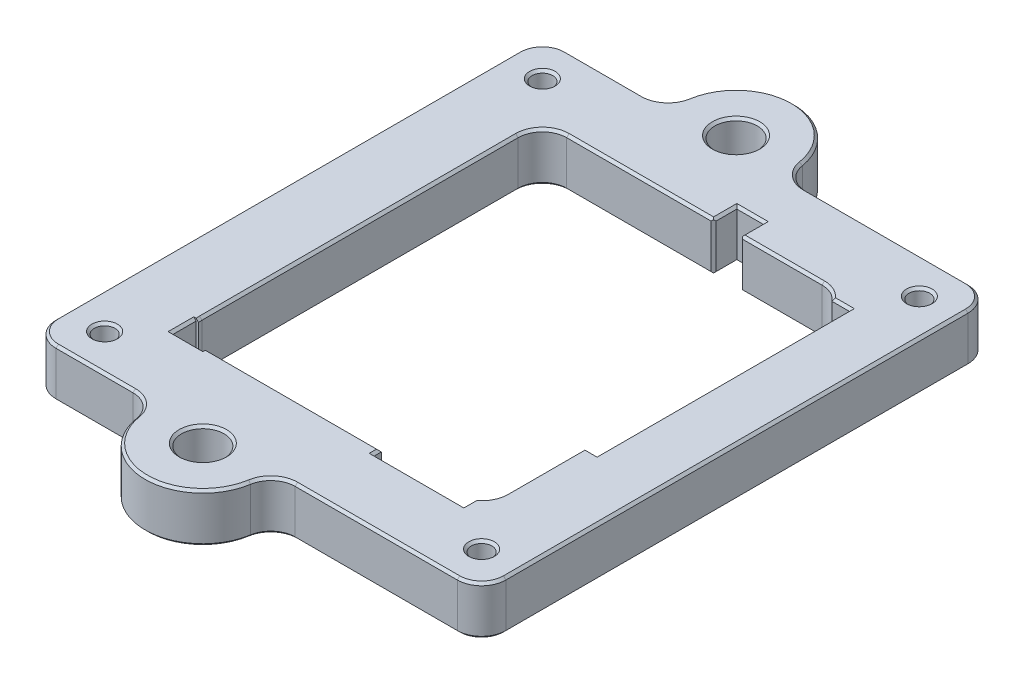
SolidWorks part; units mm, degrees
ref_plane "前视基准面" through (0, 0, 0) normal (0, 0, 1) x (1, 0, 0)
ref_plane "上视基准面" through (0, 0, 0) normal (0, 1, 0) x (1, 0, 0)
ref_plane "右视基准面" through (0, 0, 0) normal (1, 0, 0) x (0, 0, -1)
other "Configuration Table"
sketch "草图1" plane through (0, 0, 0) normal (0, 1, 0) x (1, 0, 0)
  line L0 (6, 6) -> (6, 36)
  line L1 (0, 0) -> (37, 0)
  line L2 (0, 0) -> (0, 42)
  line L3 (0, 42) -> (37, 42)
  line L4 (37, 0) -> (37, 42)
  line L5 (6, 36) -> (31, 36)
  line L6 (31, 6) -> (31, 36)
  line L7 (6, 6) -> (31, 6)
  circle A0 centre (3, 3) radius 0.85
  circle A1 centre (34, 3) radius 0.85
  circle A2 centre (34, 39) radius 0.85
  circle A3 centre (3, 39) radius 0.85
  dimension "D3" = 1.7
  dimension "D1" = 37
  dimension "D2" = 42
  dimension "D4" = 3
  dimension "D8" = 6
  dimension "D7" = 2
extrude "凸台-拉伸1" add sketch "草图1" along normal blind 4
sketch "草图2" plane through (0, 0, 0) normal (0, -1, 0) x (-1, 0, 0)
  line L0 (0, 42) -> (0, 0) construction
  circle A0 centre (-15, 42.925) radius 1.75
  circle A1 centre (-15, -0.925) radius 1.75
  circle A2 centre (-15, -0.925) radius 4.75
  circle A3 centre (-15, 42.925) radius 4.75
  point P6 (0, 21)
  line M10 (0, 42) -> (-37, 42)
  line M12 (-37, 0) -> (0, 0)
  dimension "D4" = 3.5
  dimension "D5" = 3.5
  dimension "D1" = 15
  dimension "D2" = 15
  dimension "D3" = 43.85
  dimension "D6" = 21.925
  dimension "D7" = 3
extrude "凸台-拉伸2" add sketch "草图2" against normal blind 4 contours A2 A1 M12 | A3 A0 M10
sketch "草图3" plane through (0, 0, 0) normal (0, -1, 0) x (-1, 0, 0)
  circle A0 centre (-15, -0.925) radius 1.75
  circle A1 centre (-15, 42.925) radius 1.75
extrude "切除-拉伸1" cut sketch "草图3" against normal blind 4
fillet "圆角1" radius 2 12 edges at (31, 2, -6) (31, 2, -36) (6, 2, -36) (6, 2, -6) (10.3409, 2, -42) (19.6591, 2, -42) (37, 2, -42) (37, 2, 0) (19.6591, 2, 0) (10.3409, 2, 0) (0, 2, -42) (0, 2, 0)
chamfer "倒角1" distance 0.2 angle 45 60 edges at (3, 4, -38.15) (3, 0, -38.15) (34, 4, -38.15) (34, 0, -38.15) (34, 4, -2.15) (34, 0, -2.15) (30.4142, 4, -6.5858) (30.4142, 0, -6.5858) (31, 0, -21) (31, 4, -21) (30.4142, 4, -35.4142) (30.4142, 0, -35.4142) (18.5, 0, -36) (18.5, 4, -36) (6.5858, 4, -35.4142) (6.5858, 0, -35.4142) (6, 0, -21) (6, 4, -21) (6.5858, 4, -6.5858) (6.5858, 0, -6.5858) (18.5, 4, -6) (18.5, 0, -6) (36.4142, 4, -0.5858) (36.4142, 0, -0.5858) (28.3319, 0, 0) (28.3319, 4, 0) (20.3671, 4, 0.4773) (20.3671, 0, 0.4773) (15, 0, 5.675) (15, 4, 5.675) (9.6329, 4, 0.4773) (9.6329, 0, 0.4773) (5.1681, 0, 0) (5.1681, 4, 0) (0.5858, 4, -0.5858) (0.5858, 0, -0.5858) (0, 4, -21) (0, 0, -21) (0.5858, 4, -41.4142) (0.5858, 0, -41.4142) (5.1681, 0, -42) (5.1681, 4, -42) (9.6329, 4, -42.4773) (9.6329, 0, -42.4773) (15, 0, -47.675) (15, 4, -47.675) (20.3671, 4, -42.4773) (20.3671, 0, -42.4773) (28.3319, 0, -42) (28.3319, 4, -42) (36.4142, 4, -41.4142) (36.4142, 0, -41.4142) (37, 0, -21) (37, 4, -21) (3, 4, -2.15) (3, 0, -2.15) (15, 0, -0.825) (15, 4, -0.825) (15, 0, -44.675) (15, 4, -44.675)
sketch "草图4" plane through (0, 4, 0) normal (0, 1, 0) x (1, 0, 0)
  line L0 (31, 8) -> (31, 34) construction
  line L1 (32, 14.4995) -> (28.6509, 14.4995)
  line L2 (32, 14.4995) -> (32, 35.254)
  line L3 (32, 35.254) -> (28.6509, 35.254)
  line L4 (28.6509, 14.4995) -> (28.6509, 35.254)
  dimension "D1" = 1
extrude "切除-拉伸2" cut sketch "草图4" against normal through all
sketch "草图5" plane through (0, 4, 0) normal (0, 1, 0) x (1, 0, 0)
  line L0 (29, 36) -> (8, 36) construction
  line L1 (22.2593, 36) -> (20.0779, 36)
  line L2 (22.2593, 36) -> (22.2593, 37.9117)
  line L3 (22.2593, 37.9117) -> (20.0779, 37.9117)
  line L4 (20.0779, 36) -> (20.0779, 37.9117)
  line L5 (29, 5.8) -> (8, 5.8) construction
  line L6 (8.477, 5.8) -> (5.8198, 5.8)
  line L7 (8.477, 5.8) -> (8.477, 7.7056)
  line L8 (8.477, 7.7056) -> (5.8198, 7.7056)
  line L9 (5.8198, 5.8) -> (5.8198, 7.7056)
  arc A0 (5.8, 8) -> (8, 5.8) centre (8, 8) ccw construction
extrude "切除-拉伸3" cut sketch "草图5" against normal through all
sketch "草图6" plane through (0, 4, 0) normal (0, 1, 0) x (1, 0, 0)
  line L0 (8.477, 6) -> (29, 6) construction
  line L1 (30.1414, 7.6719) -> (22.758, 7.6719)
  line L2 (30.1414, 7.6719) -> (30.1414, 5.4)
  line L3 (30.1414, 5.4) -> (22.758, 5.4)
  line L4 (22.758, 7.6719) -> (22.758, 5.4)
  dimension "D1" = 0.6
extrude "切除-拉伸4" cut sketch "草图6" against normal through all
chamfer "倒角2" distance 0.2 angle 45 34 edges at (31.1, 0.1, -14.4995) (31.1, 3.9, -14.4995) (32, 0, -24.8767) (31.6, 0, -14.4995) (31.4038, 0, -35.254) (31.6, 4, -14.4995) (32, 4, -24.8767) (31.4038, 4, -35.254) (20.0779, 0.1, -36.1) (22.2593, 0.1, -36.1) (22.2593, 3.9, -36.1) (20.0779, 3.9, -36.1) (22.2593, 0, -37.0559) (22.2593, 2, -36) (20.0779, 0, -37.0559) (20.0779, 2, -36) (21.1686, 0, -37.9117) (22.2593, 4, -37.0559) (21.1686, 4, -37.9117) (20.0779, 4, -37.0559) (5.8198, 0, -6.7528) (5.8198, 4, -6.7528) (22.758, 0.1, -5.9) (22.758, 3.9, -5.9) (30.1414, 0, -5.7596) (26.4497, 0, -5.4) (22.758, 0, -5.6) (22.758, 4, -5.6) (26.4497, 4, -5.4) (30.1414, 4, -5.7596)
equation "\"D1@草图1\"=31+6"
equation "\"D2@草图1\"=36+6"
equation "\"D6@草图2\"=\"D3@草图2\"/2"
